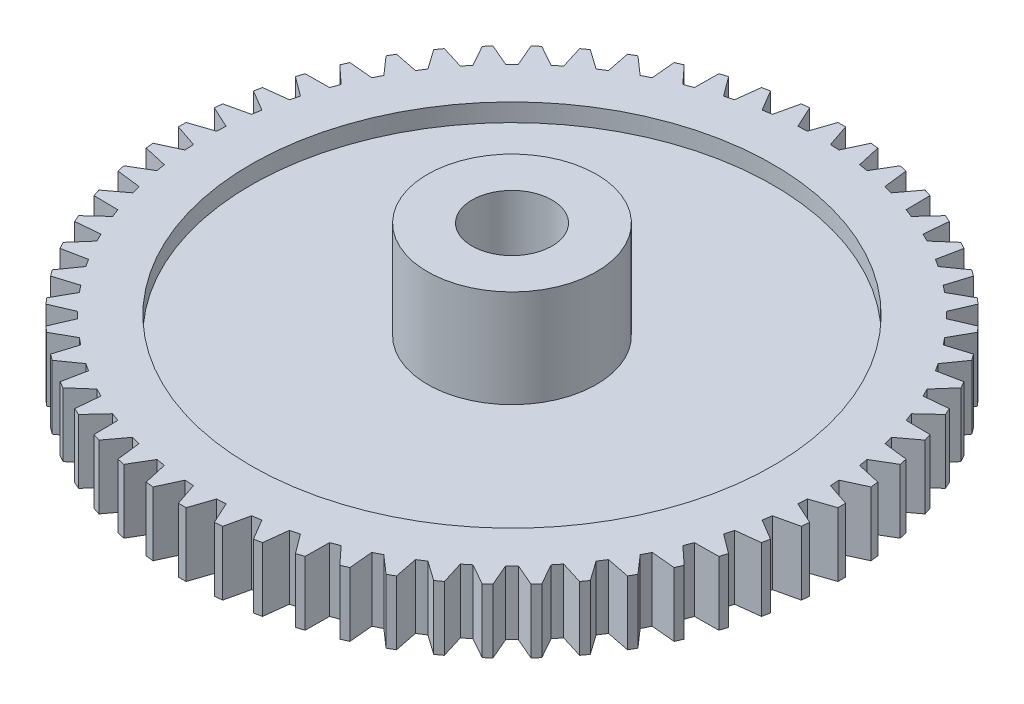
SolidWorks part; units mm, degrees
ref_plane "Front Plane" through (0, 0, 0) normal (0, 0, 1) x (1, 0, 0)
ref_plane "Top Plane" through (0, 0, 0) normal (0, 1, 0) x (1, 0, 0)
ref_plane "Right Plane" through (0, 0, 0) normal (1, 0, 0) x (0, 0, -1)
sketch "Sketch1" plane through (0, 0, 0) normal (0, 1, 0) x (1, 0, 0)
  circle A0 centre (0, 0) radius 32.7279 construction
  circle A1 centre (0, 0) radius 30.48
  circle A2 centre (0, 0) radius 3.9688
  circle A3 centre (0, 0) radius 8.382
  circle A4 centre (0, 0) radius 25.908
  dimension "D1" = 65.4558
  dimension "D2" = 60.96
  dimension "D3" = 7.9375
  dimension "D4" = 16.764
  dimension "D5" = 51.816
extrude "Boss-Extrude1" add sketch "Sketch1" along normal blind 6.35 contours A0 A1 | A1 A3 | A4 A3 region at (-29.6179, 0, 0) region at (-25.1752, 0, 0)
extrude "Boss-Extrude2" add sketch "Sketch1<3>" along normal blind 14.2621 contours A3 A2 region at (-8.1449, 0, 0)
sketch "Sketch1<3>" plane through (0, 0, 0) normal (0, 1, 0) x (1, 0, 0) same geometry as "Sketch1"
extrude "Cut-Extrude1" cut sketch "Sketch1<4>" along normal blind 1.778 contours A4 A3 region at (-25.1752, 0, 0)
sketch "Sketch1<4>" plane through (0, 0, 0) normal (0, 1, 0) x (1, 0, 0) same geometry as "Sketch1"
extrude "Cut-Extrude3" cut sketch "Sketch1<8>" against normal blind 1.778 from offset 6.35 contours A4 A3 region at (-25.1752, 0, 0)
sketch "Sketch1<8>" plane through (0, 0, 0) normal (0, 1, 0) x (1, 0, 0) same geometry as "Sketch1"
sketch "Sketch2" plane through (0, 6.35, 0) normal (0, 1, 0) x (1, 0, 0)
  line L1 (-0.381, 32.7279) -> (0.381, 32.7279)
  line L2 (-19.4346, -23.4803) -> (-0.381, 32.7279)
  line L3 (0.381, 32.7279) -> (19.4346, -23.4803)
  circle A1 centre (0, 0) radius 31.75 construction
  circle A2 centre (0, 0) radius 32.7279 construction
  circle A3 centre (0, 0) radius 30.2602
  point P10 (0, 32.7279)
  circle M11 centre (0, 0) radius 30.48
  dimension "D3" = 63.5
  dimension "D5" = 65.4558
  dimension "D4" = 0.762
extrude "Boss-Extrude3" add sketch "Sketch2" against normal blind 6.35 contours L3 L1 L2 M11 | A3 L3 L2 M11 region at (0, 6.35, -31.4121) region at (0, 6.35, -30.3612)
pattern_circular "CirPattern1" count 60 over 360 about axis through (0, 6.35, 0) along (0, -1, 0) of "Boss-Extrude3"
